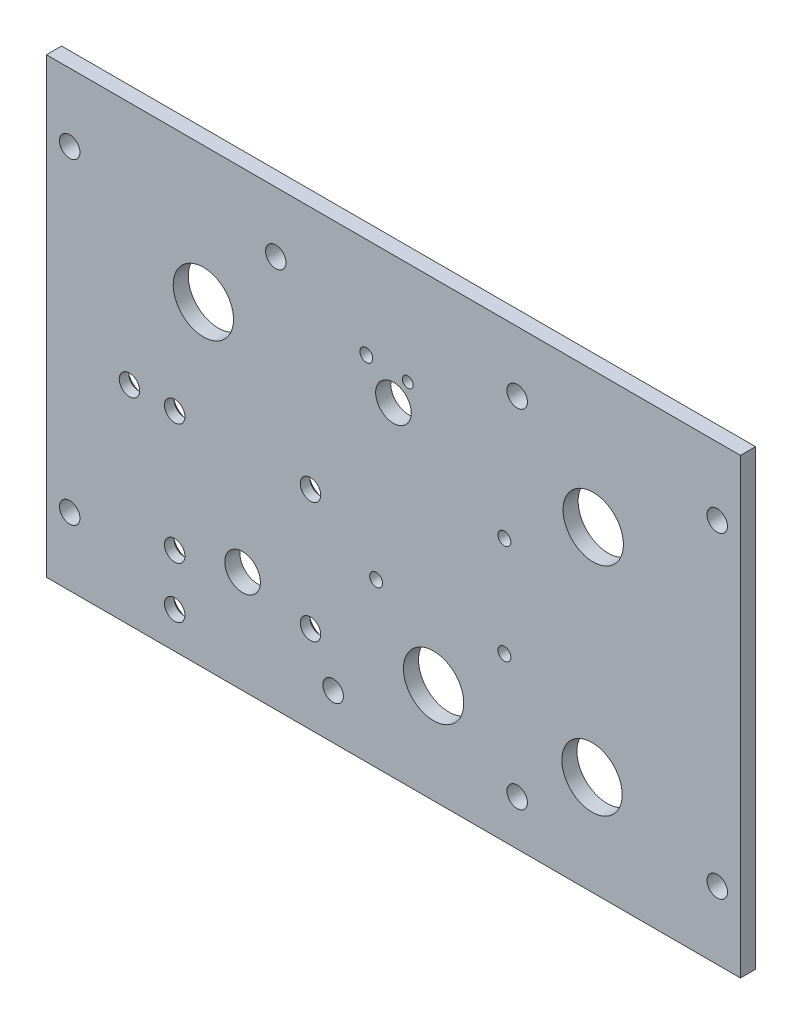
SolidWorks part; units mm, degrees
material "Acrylic (Medium-high impact)"
ref_plane "Front Plane" through (0, 0, 0) normal (0, 0, 1) x (1, 0, 0)
ref_plane "Top Plane" through (0, 0, 0) normal (0, 1, 0) x (1, 0, 0)
ref_plane "Right Plane" through (0, 0, 0) normal (1, 0, 0) x (0, 0, -1)
sketch "Sketch1" plane through (0, 0, 0) normal (0, 0, 1) x (1, 0, 0)
  line L8 (0, 95.25) -> (-146.05, 95.25)
  line L9 (-146.05, 95.25) -> (-146.05, 0)
  line L10 (-146.05, 0) -> (0, 0)
  line L11 (0, 0) -> (0, 95.25)
extrude "Boss-Extrude1" add sketch "Sketch1" against normal blind 3.175
hole_wizard "#6 Clearance Hole1" positions "Sketch3" profile "Sketch2" hole size "#6" standard "ANSI Inch" end condition through all
sketch "Sketch3" plane through (0, 0, -3.175) normal (0, 0, -1) x (-1, 0, 0)
  point P0 (4.8895, 80.9625)
  point P3 (141.1605, 80.9625)
  point P6 (141.1605, 14.2875)
  point P9 (4.8895, 14.2875)
  point P12 (46.99, 9.525)
  point P15 (85.725, 9.525)
  point P18 (97.79, 82.55)
  point P21 (46.99, 82.55)
sketch "Sketch2" plane through (-4.8895, 80.9625, -3.175) normal (1, 0, 0) x (0, 1, 0)
  line L0 (0, 0) -> (0, 3.175)
  line L1 (0, 3.175) -> (2.1526, 3.175)
  line L2 (2.1526, 3.175) -> (2.1526, 0)
  line L5 (2.1526, 0) -> (0, 0)
  line L11 (0, -6.35) -> (0, 107.95) construction
  dimension "Thru Hole Dia." = 4.3053
  dimension "Thru Hole Depth" = 3.175
sketch "Sketch5" plane through (0, 0, -7.4676) normal (0, 0, -1) x (-1, 0, 0)
  circle A0 centre (30.988, 66.675) radius 6.35
  circle A1 centre (113.03, 66.675) radius 6.35
  circle A2 centre (64.5795, 20.955) radius 6.35
  circle A3 centre (31.242, 20.955) radius 6.35
  circle A4 centre (73.025, 68.326) radius 3.75
  circle A5 centre (104.775, 21.59) radius 3.75
  dimension "D1" = 12.7
  dimension "D2" = 7.5
extrude "Cut-Extrude1" cut sketch "Sketch5" against normal through all
hole_wizard "CSK for #6 Flat Head Machine Screw (100)1" positions "Sketch7" profile "Sketch6" countersink size "#6" standard "ANSI Inch" end condition through all
sketch "Sketch7" plane through (0, 0, -3.175) normal (0, 0, -1) x (-1, 0, 0)
  point P0 (90.4875, 43.815)
  point P3 (90.4875, 18.415)
  point P6 (119.0625, 7.6362)
  point P9 (119.0625, 18.415)
  point P12 (119.0625, 43.815)
  point P15 (128.5875, 43.815)
sketch "Sketch6" plane through (-90.4875, 43.815, -3.175) normal (1, 0, 0) x (0, 1, 0)
  line L0 (0, 0) -> (0, 3.175)
  line L1 (0, 3.175) -> (2.1526, 3.175)
  line L2 (2.1526, 3.175) -> (2.1526, 1.1669)
  line L3 (2.1526, 1.1669) -> (3.5433, 0)
  line L5 (3.5433, 0) -> (0, 0)
  line L6 (-2.1526, 1.1669) -> (-3.5433, 0) construction
  line L11 (0, -6.35) -> (0, 107.95) construction
  dimension "Thru Hole Dia." = 4.3053
  dimension "Thru Hole Depth" = 3.175
  dimension "Near C'Sink Dia." = 7.0866
  dimension "Near C'Sink Angle" = 100
sketch "Sketch8" plane through (0, 0, 0) normal (0, 0, 1) x (1, 0, 0)
  circle A0 centre (-70.0124, 73.6066) radius 1.1345
extrude "Cut-Extrude2" cut sketch "Sketch8" against normal through all
hole_wizard "CSK for #2 Flat Head Machine Screw (100)1" positions "Sketch13" profile "Sketch14" countersink size "#2" standard "ANSI Inch" end condition through all
sketch "Sketch13" plane through (0, 0, -3.175) normal (0, 0, -1) x (-1, 0, 0)
  point P0 (49.68, 55.2646)
  point P3 (49.68, 34.2646)
  point P6 (76.68, 34.2646)
  point P9 (78.74, 74.1719)
sketch "Sketch14" plane through (-49.68, 55.2646, -3.175) normal (1, 0, 0) x (0, 1, 0)
  line L0 (0, 0) -> (0, 3.175)
  line L1 (0, 3.175) -> (1.3525, 3.175)
  line L2 (1.3525, 3.175) -> (1.3525, 0.698)
  line L3 (1.3525, 0.698) -> (2.1844, 0)
  line L5 (2.1844, 0) -> (0, 0)
  line L6 (-1.3525, 0.698) -> (-2.1844, 0) construction
  line L11 (0, -6.35) -> (0, 107.95) construction
  dimension "Thru Hole Dia." = 2.7051
  dimension "Thru Hole Depth" = 3.175
  dimension "Near C'Sink Dia." = 4.3688
  dimension "Near C'Sink Angle" = 100
